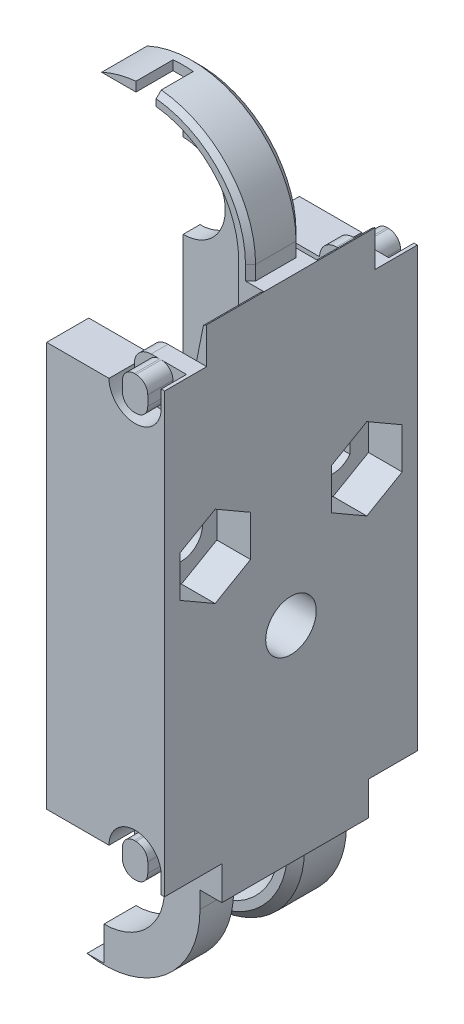
SolidWorks part; units mm, degrees
ref_plane "前视基准面" through (0, 0, 0) normal (0, 0, 1) x (1, 0, 0)
ref_plane "上视基准面" through (0, 0, 0) normal (0, 1, 0) x (1, 0, 0)
ref_plane "右视基准面" through (0, 0, 0) normal (1, 0, 0) x (0, 0, -1)
other "Configuration Table"
sketch "草图1" plane through (0, 0, 0) normal (0, 0, 1) x (1, 0, 0)
  line L0 (6.2, 9) -> (6.2, 0) construction
  line L1 (0, 0) -> (12.4, 0)
  line L2 (0, 0) -> (0, 9)
  line L4 (12.4, 0) -> (12.4, 9)
  arc A0 (0, 9) -> (12.4, 9) centre (6.2, 9) cw
  circle A1 centre (6.2, 9) radius 2.5
  circle A2 centre (1.95, 3.5) radius 0.65
  circle A3 centre (10.45, 3.5) radius 0.65
  dimension "D1" = 12.4
  dimension "D3" = 5
  dimension "D4" = 1.3
  dimension "D2" = 9
  dimension "D5" = 8.5
  dimension "D6" = 5.5
extrude "凸台-拉伸1" add sketch "草图1" along normal blind 1
sketch "草图2" plane through (0, 0, 1) normal (0, 0, 1) x (1, 0, 0)
  line L0 (0.7, 9) -> (0.7, 0)
  line L1 (0, 0) -> (12.4, 0) construction
  line L2 (11.7, 9) -> (11.7, 0)
  line L6 (0, 9) -> (0, 0)
  line L7 (0, 0) -> (12.4, 0)
  line L8 (12.4, 0) -> (12.4, 9)
  line L9 (0, 9) -> (0, 0)
  line L10 (0, 0) -> (12.4, 0)
  line L11 (12.4, 0) -> (12.4, 9)
  circle A0 centre (6.2, 9) radius 5.5
  arc A2 (12.4, 9) -> (0, 9) centre (6.2, 9) ccw
  arc A3 (12.4, 9) -> (0, 9) centre (6.2, 9) ccw
  line M5 (0, 9) -> (0, 0)
  line M6 (0, 0) -> (12.4, 0)
  line M7 (12.4, 0) -> (12.4, 9)
  arc M8 (12.4, 9) -> (0, 9) centre (6.2, 9) ccw
  dimension "D1" = 11
  dimension "D2" = 0
extrude "凸台-拉伸2" add sketch "草图2" along normal blind 2.2 contours A0 L2 L0 M6 M7 M8 M5 region at (0.5038, 4.5, 1)
sketch "草图3" plane through (0, 0, 3.2) normal (0, 0, 1) x (1, 0, 0)
  line L0 (6.2, 0) -> (6.2, 14.5) construction
  line L1 (5.6, 15.6668) -> (6.8, 15.6668)
  line L2 (5.6, 15.6668) -> (5.6, 13.6792)
  line L3 (5.6, 13.6792) -> (6.8, 13.6792)
  line L4 (6.8, 15.6668) -> (6.8, 13.6792)
  line L5 (0.7, 0) -> (11.7, 0) construction
  arc A0 (11.7, 9) -> (0.7, 9) centre (6.2, 9) ccw construction
  dimension "D1" = 1.2
extrude "切除-拉伸1" cut sketch "草图3" against normal up to surface (2.2 mm away) up to face at (6.2, 5.875, 1)
sketch "草图16" plane through (0, 0, 3.2) normal (0, 0, 1) x (1, 0, 0)
  line L0 (6.2, 0) -> (6.2, 15.1709) construction
  line L2 (13.2, 0) -> (-0.8, 0)
  line L3 (13.2, 0) -> (13.2, 5)
  line L4 (13.2, 5) -> (-0.8, 5)
  line L5 (6.8, 14.4672) -> (6.8, 15.1709)
  line L6 (5.6, 15.1709) -> (5.6, 14.4672)
  line L7 (0.7, 9) -> (0.7, 0)
  line L8 (0.7, 0) -> (11.7, 0)
  line L9 (11.7, 0) -> (11.7, 9)
  line L10 (6.8, 14.4672) -> (6.8, 15.1709)
  line L11 (5.6, 15.1709) -> (5.6, 14.4672)
  line L12 (0.7, 9) -> (0.7, 0)
  line L13 (0.7, 0) -> (11.7, 0)
  line L14 (11.7, 0) -> (11.7, 9)
  line L15 (-0.8, 0) -> (-0.8, 5)
  line L16 (-0.8, 0) -> (13.2, 0)
  line L17 (-0.8, 0) -> (-0.8, -19)
  line L18 (-0.8, -19) -> (13.2, -19)
  line L19 (13.2, 0) -> (13.2, -19)
  arc A3 (11.7, 9) -> (6.8, 14.4672) centre (6.2, 9) ccw
  arc A4 (6.8, 15.1709) -> (5.6, 15.1709) centre (6.2, 9) ccw
  arc A5 (5.6, 14.4672) -> (0.7, 9) centre (6.2, 9) ccw
  arc A6 (11.7, 9) -> (6.8, 14.4672) centre (6.2, 9) ccw
  arc A7 (6.8, 15.1709) -> (5.6, 15.1709) centre (6.2, 9) ccw
  arc A8 (5.6, 14.4672) -> (0.7, 9) centre (6.2, 9) ccw
  line M18 (11.7, 0) -> (12.4, 0)
  line M19 (12.4, 0) -> (12.4, 9)
  dimension "D2" = 5
  dimension "D3" = 14
  dimension "D4" = 19
  dimension "D1" = 0
extrude "凸台-拉伸11" add sketch "草图16" along normal blind 5.9 and the other way blind 9.1 contours L19 L2 L16 L17 L18 M18 | L15 L2 L12 L4 | L3 L4 L2 M19 region at (6.2, -9.5, 3.2) region at (12.8, 2.5, 3.2) region at (-0.05, 2.5, 3.2)
sketch "草图17" plane through (0, 0, -5.9) normal (0, 0, -1) x (-1, 0, 0)
  line L8 (-13.2, 5) -> (-13.2, -19)
  line L9 (-13.2, -19) -> (0.8, -19)
  line L10 (0.8, -19) -> (0.8, 5)
  line L11 (0.8, 5) -> (-0.7, 5)
  line L12 (-0.7, 5) -> (-0.7, 0)
  line L13 (-0.7, 0) -> (-12.4, 0)
  line L14 (-12.4, 0) -> (-12.4, 5)
  line L15 (-12.4, 5) -> (-13.2, 5)
  line L16 (-13.2, 5) -> (-13.2, -19)
  line L17 (-13.2, -19) -> (0.8, -19)
  line L18 (0.8, -19) -> (0.8, 5)
  line L19 (0.8, 5) -> (-0.7, 5)
  line L20 (-0.7, 5) -> (-0.7, 0)
  line L21 (-0.7, 0) -> (-12.4, 0)
  line L22 (-12.4, 0) -> (-12.4, 5)
  line L23 (-12.4, 5) -> (-13.2, 5)
  arc A1 (-11.9, 9) -> (-0.5, 9) centre (-6.2, 9) ccw
  circle A2 centre (-6.2, 9) radius 7.7
  line M14 (-0.7, 0) -> (-12.4, 0)
  line M15 (-12.4, 0) -> (-12.4, 5)
  dimension "D1" = 2
  dimension "D2" = 0
extrude "凸台-拉伸12" add sketch "草图17" against normal up to surface (5.9 mm away) contours A2 L20 M15 M14 region at (6.8572, 1.2193, -5.9) up to face at (5.5143, 5.6, 0)
sketch "草图18" plane through (0, 0, 9.1) normal (0, 0, 1) x (1, 0, 0)
  line L8 (13.2, -19) -> (13.2, 5)
  line L9 (13.2, 5) -> (12.4, 5)
  line L10 (12.4, 5) -> (12.4, 0)
  line L11 (12.4, 0) -> (0.7, 0)
  line L12 (0.7, 0) -> (0.7, 5)
  line L13 (0.7, 5) -> (-0.8, 5)
  line L14 (-0.8, 5) -> (-0.8, -19)
  line L15 (-0.8, -19) -> (13.2, -19)
  line L16 (13.2, -19) -> (13.2, 5)
  line L17 (13.2, 5) -> (12.4, 5)
  line L18 (12.4, 5) -> (12.4, 0)
  line L19 (12.4, 0) -> (0.7, 0)
  line L20 (0.7, 0) -> (0.7, 5)
  line L21 (0.7, 5) -> (-0.8, 5)
  line L22 (-0.8, 5) -> (-0.8, -19)
  line L23 (-0.8, -19) -> (13.2, -19)
  arc A1 (0.5, 9) -> (11.9, 9) centre (6.2, 9) ccw
  circle A2 centre (6.2, 9) radius 7.7
  line M12 (12.4, 0) -> (0.7, 0)
  line M13 (0.7, 0) -> (0.7, 5)
  dimension "D1" = 2
  dimension "D2" = 0
extrude "凸台-拉伸13" add sketch "草图18" against normal blind 5.1 contours A2 L18 M13 M12 region at (6.8572, 1.2193, 9.1)
sketch "草图19" plane through (-0.8, 0, 0) normal (-1, 0, 0) x (0, 0, 1)
  line L0 (-5.9, 4.4338) -> (-5.9, 1.3) construction
  line L1 (-5.9, 5) -> (-3.4, 5)
  line L2 (-5.9, 5) -> (-5.9, 1.3)
  line L3 (-5.9, 1.3) -> (-3.4, 1.3)
  line L4 (-3.4, 5) -> (-3.4, 1.3)
  line L5 (9.1, 5) -> (6.6, 5)
  line L6 (9.1, 5) -> (9.1, 1.3)
  line L7 (9.1, 1.3) -> (6.6, 1.3)
  line L8 (6.6, 5) -> (6.6, 1.3)
  line L9 (-5.9, 4.4338) -> (-5.9, 1.3)
  line M5 (9.1, -19) -> (9.1, 5)
  line M6 (9.1, 5) -> (-5.9, 5)
  line M7 (-5.9, 5) -> (-5.9, -19)
  dimension "D1" = 2.5
  dimension "D2" = 2.5
extrude "凸台-拉伸14" add sketch "草图19" against normal up to surface (14 mm away) contours L8 L7 M6 M5 | L4 L2 L3 M6 M7 region at (-0.8, 3.15, 7.85) region at (-0.8, 3.15, -4.65) up to face at (13.2, -7, 1.6)
ref_plane "基准面2" through (0, 0, 1.6) normal (0, 0, -1) x (-1, 0, 0)
sketch "草图21" plane through (0, 0, 1.6) normal (0, 0, -1) x (-1, 0, 0)
  line L0 (0.8, -19) -> (-13.2, -19) construction
  line L1 (-11.9, -19) -> (-0.5, -19)
  line L2 (-11.9, -19) -> (-11.9, -23)
  line L4 (-0.5, -19) -> (-0.5, -23)
  line L5 (-6.2, -19) -> (-6.2, 5) construction
  line L9 (0.8, 5) -> (-13.2, 5)
  line L10 (-13.2, 5) -> (-13.2, -19)
  line L11 (-13.2, -19) -> (0.8, -19)
  line L12 (0.8, -19) -> (0.8, 5)
  line L13 (0.8, 5) -> (-13.2, 5)
  line L14 (-13.2, 5) -> (-13.2, -19)
  line L15 (-13.2, -19) -> (0.8, -19)
  line L16 (0.8, -19) -> (0.8, 5)
  arc A0 (-11.9, -23) -> (-0.5, -23) centre (-6.2, -23) ccw
  circle A1 centre (-6.2, -23) radius 3.6
  dimension "D4" = 7.2
  dimension "D2" = 11.4
  dimension "D3" = 4
  dimension "D1" = 0
extrude "凸台-拉伸15" add sketch "草图21" along normal blind 2.5 from offset 1.6 contours L2 A0 L4 L15 L1 A1 region at (6.2, -19.1497, 1.6)
sketch "草图22" plane through (0, 0, 0) normal (0, 0, 1) x (1, 0, 0)
  circle A0 centre (6.2, -23) radius 4.2
  circle M2 centre (6.2, -23) radius 3.6
  line M4 (11.9, -19) -> (0.5, -19)
  dimension "D1" = 8.4
extrude "切除-拉伸6" cut sketch "草图22" against normal blind 0.6 and the other way blind 2.5 contours A0 M4 M2 | M2 | A0 M4 region at (3.7932, -26.2977, 0) region at (6.2, -18.9198, 0) region at (6.2, -23, 0)
chamfer "倒角2" distance 0.5 angle 45 1 edges at (6.2, -27.2, 0)
mirror "镜向1" about plane through (0, 0, 1.6) normal (0, 0, -1) of "倒角2", "切除-拉伸6", "凸台-拉伸15"
sketch "草图23" plane through (0, 0, 1.6) normal (0, 0, -1) x (-1, 0, 0)
  line L0 (-11.9, -19) -> (-0.5, -19) construction
  circle A0 centre (-6.2, -24) radius 6.2
  circle A1 centre (-6.2, -24) radius 8.2
  point P5 (-6.2, -19)
  dimension "D1" = 2
  dimension "D3" = 12.4
  dimension "D2" = 5
extrude "切除-拉伸7" cut sketch "草图23" against normal mid plane 3.2 contours A0 | A1 A0 region at (6.2, -24, 1.6) region at (14.1681, -24, 1.6)
sketch "草图24" plane through (0, 0, -2.5) normal (0, 0, -1) x (-1, 0, 0)
  line L0 (-7.2, -21.2679) -> (-7.2, -24.7321)
  line L3 (-11.9, -19) -> (-11.9, -23)
  line L4 (-0.5, -23) -> (-0.5, -19)
  line L5 (-0.5, -19) -> (-11.9, -19)
  line L6 (-11.9, -19) -> (-11.9, -23)
  line L7 (-0.5, -23) -> (-0.5, -19)
  line L8 (-0.5, -19) -> (-11.9, -19)
  circle A0 centre (-6.2, -23) radius 3.6 construction
  arc A1 (-11.9, -23) -> (-0.5, -23) centre (-6.2, -23) ccw
  arc A2 (-11.9, -23) -> (-0.5, -23) centre (-6.2, -23) ccw
  circle A3 centre (-6.2, -23) radius 3.6
  circle A4 centre (-6.2, -23) radius 2
  point P11 (-7.2, -23)
  circle M6 centre (-6.2, -23) radius 3.6
  line M7 (-11.9, -19) -> (-11.9, -23)
  arc M8 (-11.9, -23) -> (-0.5, -23) centre (-6.2, -23) ccw
  line M9 (-0.5, -23) -> (-0.5, -19)
  line M10 (-0.5, -19) -> (-11.9, -19)
  dimension "D2" = 4
  dimension "D3" = 1
  dimension "D1" = 0
extrude "凸台-拉伸16" add sketch "草图24" along normal blind 0.5 contours M10 M7 M8 M9 M6 | A4 M6 | L0 A4 region at (7.61, -23, -2.5) region at (6.2, -19.1497, -2.5) region at (9.6982, -23, -2.5)
ref_plane "基准面3" through (0, 0, 1.6) normal (0, 0, -1) x (-1, 0, 0)
chamfer "倒角4" distance 2 angle 45 2 edges at (-0.8, 5, 1.6) (-0.8, -19, 1.6)
sketch "草图25" plane through (-0.8, 0, 0) normal (-1, 0, 0) x (0, 0, 1)
  line L0 (1.6, -14) -> (1.6, 0) construction
  line L1 (9.1, -7) -> (1.6, -7) construction
  line L2 (5.7, -18.3) -> (3.2, -18.3) construction
  line L3 (5.7, -18.3) -> (3.2, -18.3)
  line L4 (9.1, -17) -> (9.1, 3)
  line L5 (9.1, 3) -> (-5.9, 3)
  line L6 (-5.9, 3) -> (-5.9, -17)
  line L8 (9.1, -17) -> (9.1, 3)
  line L10 (-5.9, 3) -> (-5.9, -17)
  line L12 (4.45, -18.3) -> (4.45, -7) construction
  line L21 (9.1, 3) -> (-5.9, 3)
  line L23 (-5.9, -17) -> (9.1, -17)
  line L24 (-5.9, -17) -> (9.1, -17)
  circle A0 centre (6.1, -4) radius 1.7
  circle A1 centre (-2.9, -4) radius 1.7
  dimension "D2" = 3.4
  dimension "D3" = 7
  dimension "D4" = 3
  dimension "D1" = 0
extrude "切除-拉伸8" cut sketch "草图25" against normal blind 2 contours A1 | A0 region at (-0.8, -4, 6.1) region at (-0.8, -4, -2.9)
sketch "草图26" plane through (1.2, 0, 0) normal (-1, 0, 0) x (0, 0, 1)
  circle A0 centre (6.1, -4) radius 0.95
  circle A1 centre (-2.9, -4) radius 0.95
  dimension "D1" = 1.9
extrude "切除-拉伸9" cut sketch "草图26" against normal through all
sketch "草图27" plane through (13.2, 0, 0) normal (1, 0, 0) x (0, 0, -1)
  line L0 (5.9, 5) -> (5.9, -19) construction
  line L1 (-6.1, -6.4249) -> (-4, -5.2124)
  line L2 (-4, -5.2124) -> (-4, -2.7876)
  line L3 (-4, -2.7876) -> (-6.1, -1.5751)
  line L4 (-6.1, -1.5751) -> (-8.2, -2.7876)
  line L5 (-8.2, -2.7876) -> (-8.2, -5.2124)
  line L6 (-8.2, -5.2124) -> (-6.1, -6.4249)
  line L7 (2.9, -6.4249) -> (5, -5.2124)
  line L8 (5, -5.2124) -> (5, -2.7876)
  line L9 (5, -2.7876) -> (2.9, -1.5751)
  line L10 (2.9, -1.5751) -> (0.8, -2.7876)
  line L11 (0.8, -2.7876) -> (0.8, -5.2124)
  line L12 (0.8, -5.2124) -> (2.9, -6.4249)
  circle A0 centre (-6.1, -4) radius 2.1 construction
  circle A1 centre (2.9, -4) radius 2.1 construction
  dimension "D1" = 4.2
extrude "切除-拉伸10" cut sketch "草图27" against normal blind 2
ref_plane "基准面4" through (0, 0, 1.6) normal (0, 0, 1) x (1, 0, 0)
sketch "草图30" plane through (0, 0, 9.1) normal (0, 0, 1) x (1, 0, 0)
  line L0 (-0.8, -7) -> (13.2, -7) construction
  line L1 (13.2, -28.6104) -> (6.2, -28.6104)
  line L2 (13.2, -28.6104) -> (13.2, 14.6104)
  line L3 (13.2, 14.6104) -> (6.2, 14.6104)
  line L4 (6.2, -28.6104) -> (6.2, 14.6104)
  line L6 (13.2, 5) -> (1.2, 5)
  line L8 (-0.8, 3) -> (-0.8, -17)
  line L10 (1.2, -19) -> (13.2, -19)
  line L11 (13.2, -19) -> (13.2, 5)
  line L12 (13.2, 5) -> (1.2, 5)
  line L14 (-0.8, 3) -> (-0.8, -17)
  line L16 (1.2, -19) -> (13.2, -19)
  line L17 (13.2, -19) -> (13.2, 5)
  line L18 (13.2, -28.6104) -> (-7.3517, -28.6104)
  line L19 (13.2, -28.6104) -> (13.2, 14.6104)
  line L20 (13.2, 14.6104) -> (-7.3517, 14.6104)
  line L21 (-7.3517, -28.6104) -> (-7.3517, 14.6104)
  line L25 (1.2, 5) -> (-0.8, 3)
  line L27 (1.2, 5) -> (-0.8, 3)
  line L29 (-0.8, -17) -> (1.2, -19)
  line L30 (-0.8, -17) -> (1.2, -19)
  point P12 (6.2, -7)
  line M11 (13.2, 5) -> (1.2, 5)
  line M12 (1.2, 5) -> (-0.8, 3)
  line M13 (-0.8, 3) -> (-0.8, -17)
  line M14 (-0.8, -17) -> (1.2, -19)
  line M15 (1.2, -19) -> (13.2, -19)
  dimension "D1" = 0
extrude "切除-拉伸11" cut sketch "草图30" against normal through all contours L21 L18 L4 L14 L20 M15 M14 M13 M12 M11 | L0 L4 M13 M11 M12 | L0 L14 L4 M14 M15 region at (2.7691, -1.1301, 9.1) region at (-1.8767, -7, 9.1) region at (2.7691, -12.8699, 9.1)
sketch "草图31" plane through (6.2, 0, 0) normal (-1, 0, 0) x (0, 0, 1)
  line L0 (3.2, 0) -> (1, 0) construction
  line L1 (-3.9, 0) -> (7.1, 0)
  line L2 (-3.9, 0) -> (-3.9, -13.8)
  line L3 (-3.9, -13.8) -> (7.1, -13.8)
  line L4 (7.1, 0) -> (7.1, -13.8)
  line L5 (-5.9, -19) -> (-5.9, 5) construction
  line L6 (9.1, -19) -> (9.1, 5) construction
  line L7 (3.2, -15.8) -> (0, -15.8) construction
  dimension "D1" = 2
  dimension "D2" = 2
  dimension "D3" = 2
extrude "切除-拉伸12" cut sketch "草图31" against normal blind 5
sketch "草图32" plane through (11.2, 0, 0) normal (-1, 0, 0) x (0, 0, 1)
  line L0 (1.6, 7.7) -> (1.6, -7.7) construction
  line L1 (-3.9, -13.8) -> (7.1, -13.8) construction
  circle A0 centre (1.6, -9.8) radius 1.5
  dimension "D1" = 4
  dimension "D2" = 3
extrude "切除-拉伸13" cut sketch "草图32" against normal blind 5
sketch "草图33" plane through (0, -19, 0) normal (0, -1, 0) x (1, 0, 0)
  line L0 (6.2, 9.1) -> (13.2, 9.1) construction
  line L1 (6.2, 5.7) -> (6.2, 9.1) construction
  circle A0 centre (8.5, 6.8) radius 1.4
  dimension "D1" = 2.8
  dimension "D2" = 2.3
  dimension "D3" = 2.3
extrude "切除-拉伸16" cut sketch "草图33" against normal blind 8
chamfer "倒角5" distance 1 angle 45 1 edges at (8.5, -11, 7.1)
sketch "草图35" plane through (0, 0, 9.1) normal (0, 0, 1) x (1, 0, 0)
  line L0 (12.4, 5) -> (12.4, 9)
  line L1 (12.4, 9) -> (11.9, 9)
  line L2 (11.9, 9) -> (8.4, 5)
  line L3 (13.2, 5) -> (6.2, 5) construction
  line L4 (12.4, 5) -> (6.2, 5) construction
  line L5 (12.4, 5) -> (6.2, 5)
  line L6 (12.4, 9) -> (13.2, 5)
  line L7 (13.2, 5) -> (12.4, 5)
  line M6 (13.2, 5) -> (6.2, 5)
  dimension "D1" = 4
  dimension "D2" = 0.5
  dimension "D3" = 4
extrude "凸台-拉伸17" add sketch "草图35" against normal blind 2.5 contours L1 L2 L0 M6 | L6 L0 M6 region at (11.0481, 6.4815, 9.1) region at (12.6667, 6.3333, 9.1)
mirror "镜向3" about plane through (0, 0, 1.6) normal (0, 0, 1) of "凸台-拉伸17"
sketch "草图36" plane through (0, 0, 6.6) normal (0, 0, -1) x (-1, 0, 0)
  line L1 (-12.4, 9) -> (-11.9, 9) construction
  line L2 (-12.4, 9) -> (-13.2, 5) construction
  line L5 (-13.2, 5) -> (-13.2, 9)
  line L6 (-13.2, 9) -> (-12.4, 9) construction
  line L7 (-12.4, 5) -> (-13.2, 5)
  line L8 (-12.4, 5) -> (-13.2, 9)
  line L10 (-12.4, 9) -> (-12.4, 5) construction
extrude "凸台-拉伸18" add sketch "草图36" along normal up to surface (10 mm away) up to face at (10.4342, 5.3744, -3.4)
sketch "草图38" plane through (0, 0, 9.1) normal (0, 0, 1) x (1, 0, 0)
  line L0 (13.2, -19) -> (13.2, -22)
  line L1 (13.2, -22) -> (12.2, -22)
  line L2 (12.2, -22) -> (9.7, -19)
  line L3 (6.2, -19) -> (13.2, -19) construction
  line L4 (13.2, -19) -> (9.7, -19)
  line M4 (6.2, -19) -> (13.2, -19)
  dimension "D1" = 1
  dimension "D2" = 3
extrude "凸台-拉伸19" add sketch "草图38" against normal blind 3.4 contours L2 L1 L0 M4 region at (11.9593, -20.2222, 9.1)
mirror "镜向6" about plane through (0, 0, 1.6) normal (0, 0, 1) of "凸台-拉伸19"
sketch "草图39" plane through (0, 0, 5.7) normal (0, 0, -1) x (-1, 0, 0)
  line L0 (-11.9, -19) -> (-13.2, -19)
  line L1 (-13.2, -19) -> (-13.2, -22)
  line L2 (-13.2, -22) -> (-11.9, -19)
extrude "凸台-拉伸20" add sketch "草图39" along normal up to surface (8.2 mm away) up to face at (12.48, -20.728, -2.5)
sketch "草图40" plane through (0, 5, 0) normal (0, 1, 0) x (1, 0, 0)
  line L1 (8.4, -6.6) -> (16.8775, -6.6)
  line L2 (8.4, -6.6) -> (8.4, -9.6779)
  line L3 (8.4, -9.6779) -> (16.8775, -9.6779)
  line L4 (16.8775, -6.6) -> (16.8775, -9.6779)
  line L5 (8.4, 3.4) -> (14.8256, 3.4)
  line L6 (8.4, 3.4) -> (8.4, 6.7357)
  line L7 (8.4, 6.7357) -> (14.8256, 6.7357)
  line L8 (14.8256, 3.4) -> (14.8256, 6.7357)
extrude "切除-拉伸17" cut sketch "草图40" along normal up to surface (4 mm away) up to face at (12.15, 9, 7.85)
sketch "草图42" plane through (0, -19, 0) normal (0, -1, 0) x (1, 0, 0)
  line L1 (9.7, -3) -> (14.9483, -3)
  line L2 (9.7, -3) -> (9.7, -6.6318)
  line L3 (9.7, -6.6318) -> (14.9483, -6.6318)
  line L4 (14.9483, -3) -> (14.9483, -6.6318)
  line L5 (9.7, 5.7) -> (16.4897, 5.7)
  line L6 (9.7, 5.7) -> (9.7, 10.2612)
  line L7 (9.7, 10.2612) -> (16.4897, 10.2612)
  line L8 (16.4897, 5.7) -> (16.4897, 10.2612)
extrude "切除-拉伸18" cut sketch "草图42" along normal up to surface (3 mm away) up to face at (12.7, -22, 7.4)
sketch "草图43" plane through (0, 0, 9.1) normal (0, 0, 1) x (1, 0, 0)
  line L0 (7.1, -19) -> (9.9, -19) construction
  line L1 (7.1, -19) -> (9.9, -19)
  line L3 (10.7, -19) -> (12.2, -19)
  line L4 (6.2, -19) -> (13.2, -19)
  line L5 (13.2, -19) -> (13.2, 5)
  line L6 (13.2, 5) -> (6.2, 5)
  line L7 (6.2, 5) -> (6.2, -19)
  line L8 (6.2, -19) -> (13.2, -19)
  line L9 (13.2, -19) -> (13.2, 5)
  line L10 (13.2, 5) -> (6.2, 5)
  line L11 (6.2, 5) -> (6.2, -19)
  line L12 (10.7, -19) -> (10.7, -18.7)
  line L13 (11.4, -18) -> (11.5, -18)
  line L14 (12.2, -19) -> (12.2, -18.7)
  arc A0 (11.5, -18) -> (12.2, -18.7) centre (11.5, -18.7) cw
  arc A1 (10.7, -18.7) -> (11.4, -18) centre (11.4, -18.7) cw
  arc A2 (9.9, -19) -> (13, -19) centre (11.45, -19) cw
  point P12 (12.2, -18)
  point P15 (10.7, -18)
  line M7 (6.2, -19) -> (13.2, -19)
  dimension "D5" = 0.7
  dimension "D2" = 1
  dimension "D3" = 1.5
  dimension "D4" = 1
  dimension "D1" = 0
extrude "切除-拉伸19" cut sketch "草图43" against normal blind 1.5 contours A2 L12 A1 L13 A0 L14 M7 region at (11.45, -17.4847, 9.1)
mirror "镜向7" about plane through (0, 0, 1.6) normal (0, 0, -1) of "切除-拉伸19"
ref_plane "基准面5" through (0, -7, 0) normal (0, 1, 0) x (1, 0, 0)
mirror "镜向8" about plane through (0, -7, 0) normal (0, 1, 0) of "镜向7", "切除-拉伸19"
chamfer "倒角6" distance 0.5 angle 45 4 edges at (11.9, -21, 3.2) (9.8573, -27.372, 3.2) (11.9, -21, 0) (9.8573, -27.372, 0)
chamfer "倒角7" distance 0.5 angle 45 2 edges at (6.8481, -18.8503, 3.2) (6.8481, -18.8503, 0)
chamfer "倒角8" distance 0.3 angle 45 2 edges at (12.4, 7, 3.2) (10.7913, 13.1665, 3.2)
chamfer "倒角9" distance 0.5 angle 45 2 edges at (12.4, 7, 0) (9.5226, 14.2346, 0)
chamfer "倒角10" distance 1 angle 45 1 edges at (13.2, 9, 1.6) first distance on face at (12.5625, 5.8125, 2.025)
sketch "草图44" plane through (0, 5, 0) normal (0, 1, 0) x (1, 0, 0)
  line L0 (13.2, 5.9) -> (13, 5.9) construction
  line L1 (13, 5.9) -> (13, 4.4) construction
  line L2 (13, 4.4) -> (12.2, 4.4) construction
  line L3 (12.2, 4.4) -> (12.2, 5.9) construction
  line L4 (12.2, 5.9) -> (10.7, 5.9) construction
  line L5 (10.7, 5.9) -> (10.7, 4.4) construction
  line L6 (10.7, 4.4) -> (9.9, 4.4) construction
  line L7 (9.9, 4.4) -> (9.9, 5.9) construction
  line L8 (9.9, 5.9) -> (6.2, 5.9) construction
  line L9 (6.2, 5.9) -> (6.2, 3.4) construction
  line L10 (6.2, 3.4) -> (12.4, 3.4) construction
  line L11 (12.4, 3.4) -> (13.2, 3.4) construction
  line L12 (13.2, 3.4) -> (13.2, 5.9) construction
  line L13 (9.9, -9.1) -> (9.9, -7.6) construction
  line L14 (9.9, -7.6) -> (10.7, -7.6) construction
  line L15 (10.7, -7.6) -> (10.7, -9.1) construction
  line L16 (10.7, -9.1) -> (12.2, -9.1) construction
  line L17 (12.2, -9.1) -> (12.2, -7.6) construction
  line L18 (12.2, -7.6) -> (13, -7.6) construction
  line L19 (13, -7.6) -> (13, -9.1) construction
  line L20 (13, -9.1) -> (13.2, -9.1) construction
  line L21 (13.2, -9.1) -> (13.2, -6.6) construction
  line L22 (13.2, -6.6) -> (12.4, -6.6) construction
  line L23 (12.4, -6.6) -> (6.2, -6.6) construction
  line L24 (6.2, -6.6) -> (6.2, -9.1) construction
  line L25 (6.2, -9.1) -> (9.9, -9.1) construction
  line L26 (13.2, 5.9) -> (13, 5.9)
  line L27 (13, 5.9) -> (13, 4.4)
  line L28 (13, 4.4) -> (12.2, 4.4)
  line L29 (12.2, 4.4) -> (12.2, 5.9)
  line L30 (12.2, 5.9) -> (10.7, 5.9)
  line L31 (10.7, 5.9) -> (10.7, 4.4)
  line L32 (10.7, 4.4) -> (9.9, 4.4)
  line L33 (9.9, 4.4) -> (9.9, 5.9)
  line L34 (9.9, 5.9) -> (6.2, 5.9)
  line L35 (6.2, 5.9) -> (6.2, 3.4)
  line L36 (6.2, 3.4) -> (12.4, 3.4)
  line L37 (12.4, 3.4) -> (13.2, 3.4)
  line L38 (13.2, 3.4) -> (13.2, 5.9)
  line L39 (9.9, -9.1) -> (9.9, -7.6)
  line L40 (9.9, -7.6) -> (10.7, -7.6)
  line L41 (10.7, -7.6) -> (10.7, -9.1)
  line L42 (10.7, -9.1) -> (12.2, -9.1)
  line L43 (12.2, -9.1) -> (12.2, -7.6)
  line L44 (12.2, -7.6) -> (13, -7.6)
  line L45 (13, -7.6) -> (13, -9.1)
  line L46 (13, -9.1) -> (13.2, -9.1)
  line L47 (13.2, -9.1) -> (13.2, -6.6)
  line L48 (13.2, -6.6) -> (12.4, -6.6)
  line L49 (12.4, -6.6) -> (6.2, -6.6)
  line L50 (6.2, -6.6) -> (6.2, -9.1)
  line L51 (6.2, -9.1) -> (9.9, -9.1)
  line L52 (9.9, -7.6) -> (9.9, -6.6)
  line L53 (9.9, 4.4) -> (9.9, 3.4)
  line M2 (9.9, -7.6) -> (10.7, -7.6)
  line M3 (10.7, -7.6) -> (10.7, -9.1)
  line M4 (10.7, -9.1) -> (12.2, -9.1)
  line M5 (12.2, -9.1) -> (12.2, -7.6)
  line M6 (12.2, -7.6) -> (13, -7.6)
  line M7 (13, -7.6) -> (13, -9.1)
  line M8 (13, -9.1) -> (13.2, -9.1)
  line M9 (13.2, -9.1) -> (13.2, -6.6)
  line M10 (13.2, -6.6) -> (12.4, -6.6)
  line M11 (12.4, -6.6) -> (6.2, -6.6)
extrude "凸台-拉伸21" add sketch "草图44" along normal blind 1 contours L52 M2 M3 M4 M5 M6 M7 M8 M9 M10 M11 | L32 L53 L36 L37 L38 L26 L27 L28 L29 L30 L31 region at (11.591, 5, -4.4449) region at (11.591, 5, 7.6449)
sketch "草图45" plane through (0, -19, 0) normal (0, -1, 0) x (1, 0, 0)
  line L0 (9.9, -5.9) -> (9.9, -4.4) construction
  line L1 (9.9, -4.4) -> (10.7, -4.4) construction
  line L2 (10.7, -4.4) -> (10.7, -5.9) construction
  line L3 (10.7, -5.9) -> (12.2, -5.9) construction
  line L4 (12.2, -5.9) -> (12.2, -4.4) construction
  line L5 (12.2, -4.4) -> (13, -4.4) construction
  line L6 (13, -4.4) -> (13, -5.9) construction
  line L7 (13, -5.9) -> (13.2, -5.9) construction
  line L8 (13.2, -5.9) -> (13.2, -3) construction
  line L9 (13.2, -3) -> (6.2, -3) construction
  line L10 (6.2, -3) -> (6.2, -5.9) construction
  line L11 (6.2, -5.9) -> (9.9, -5.9) construction
  line L12 (13.2, 9.1) -> (13, 9.1) construction
  line L13 (13, 9.1) -> (13, 7.6) construction
  line L14 (13, 7.6) -> (12.2, 7.6) construction
  line L15 (12.2, 7.6) -> (12.2, 9.1) construction
  line L16 (12.2, 9.1) -> (10.7, 9.1) construction
  line L17 (10.7, 9.1) -> (10.7, 7.6) construction
  line L18 (10.7, 7.6) -> (9.9, 7.6) construction
  line L19 (9.9, 7.6) -> (9.9, 9.1) construction
  line L20 (9.9, 9.1) -> (6.2, 9.1) construction
  line L21 (6.2, 9.1) -> (6.2, 5.7) construction
  line L22 (6.2, 5.7) -> (7.634, 5.7) construction
  line L23 (9.366, 5.7) -> (11.9, 5.7) construction
  line L24 (11.9, 5.7) -> (13.2, 5.7) construction
  line L25 (13.2, 5.7) -> (13.2, 9.1) construction
  line L26 (9.9, -5.9) -> (9.9, -4.4)
  line L27 (9.9, -4.4) -> (10.7, -4.4)
  line L28 (10.7, -4.4) -> (10.7, -5.9)
  line L29 (10.7, -5.9) -> (12.2, -5.9)
  line L30 (12.2, -5.9) -> (12.2, -4.4)
  line L31 (12.2, -4.4) -> (13, -4.4)
  line L32 (13, -4.4) -> (13, -5.9)
  line L33 (13, -5.9) -> (13.2, -5.9)
  line L34 (13.2, -5.9) -> (13.2, -3)
  line L35 (13.2, -3) -> (6.2, -3)
  line L36 (6.2, -3) -> (6.2, -5.9)
  line L37 (6.2, -5.9) -> (9.9, -5.9)
  line L38 (13.2, 9.1) -> (13, 9.1)
  line L39 (13, 9.1) -> (13, 7.6)
  line L40 (13, 7.6) -> (12.2, 7.6)
  line L41 (12.2, 7.6) -> (12.2, 9.1)
  line L42 (12.2, 9.1) -> (10.7, 9.1)
  line L43 (10.7, 9.1) -> (10.7, 7.6)
  line L44 (10.7, 7.6) -> (9.9, 7.6)
  line L45 (9.9, 7.6) -> (9.9, 9.1)
  line L46 (9.9, 9.1) -> (6.2, 9.1)
  line L47 (6.2, 9.1) -> (6.2, 5.7)
  line L48 (6.2, 5.7) -> (7.634, 5.7)
  line L49 (9.366, 5.7) -> (11.9, 5.7)
  line L50 (11.9, 5.7) -> (13.2, 5.7)
  line L51 (13.2, 5.7) -> (13.2, 9.1)
  line L52 (9.9, -4.4) -> (9.9, -3)
  line L54 (9.9, 7.6) -> (9.9, 5.7)
  arc A0 (9.366, 5.7) -> (7.634, 5.7) centre (8.5, 6.8) ccw construction
  arc A1 (9.366, 5.7) -> (7.634, 5.7) centre (8.5, 6.8) ccw
  line M2 (13.2, 9.1) -> (13, 9.1)
  line M3 (13, 9.1) -> (13, 7.6)
  line M4 (13, 7.6) -> (12.2, 7.6)
  line M5 (12.2, 7.6) -> (12.2, 9.1)
  line M6 (12.2, 9.1) -> (10.7, 9.1)
  line M7 (10.7, 9.1) -> (10.7, 7.6)
  line M8 (10.7, 7.6) -> (9.9, 7.6)
  line M15 (11.9, 5.7) -> (13.2, 5.7)
  line M16 (13.2, 5.7) -> (13.2, 9.1)
extrude "凸台-拉伸22" add sketch "草图45" along normal blind 1 contours L52 L27 L28 L29 L30 L31 L32 L33 L34 L35 | L54 L49 M8 M15 M16 M2 M3 M4 M5 M6 M7 region at (11.5835, -19, -4.2157) region at (11.5772, -19, 7.1415)
fillet "圆角1" radius 1 4 edges at (9.9, 6, -3.9) (9.9, 6, 7.1) (9.9, -20, 6.65) (9.9, -20, -3.7)
fillet "圆角2" radius 0.7 8 edges at (10.7, -19.9798, -5.15) (12.2, -20, -5.15) (12.2, -20, 8.35) (10.7, -19.9798, 8.35) (10.7, 5.9798, 8.35) (12.2, 6, 8.35) (12.2, 6, -5.15) (10.7, 5.9798, -5.15)
sketch "草图46" plane through (11.2, 0, 0) normal (-1, 0, 0) x (0, 0, 1)
  line L0 (-2.9, -1.5751) -> (-2.9, -6.4249)
  line L1 (6.1, -1.5751) -> (6.1, -6.4249)
  line L2 (7.1, -2.1525) -> (7.1, -5.8475)
  line L3 (-3.9, -2.1525) -> (-3.9, -5.8475)
  line L18 (7.1, -5.8475) -> (6.1, -6.4249)
  line L19 (6.1, -6.4249) -> (4, -5.2124)
  line L20 (4, -5.2124) -> (4, -2.7876)
  line L21 (4, -2.7876) -> (6.1, -1.5751)
  line L22 (6.1, -1.5751) -> (7.1, -2.1525)
  line L23 (7.1, -2.1525) -> (7.1, 0)
  line L24 (7.1, 0) -> (4, 0)
  line L25 (4, 0) -> (1, 0)
  line L26 (1, 0) -> (-3.9, 0)
  line L27 (-3.9, 0) -> (-3.9, -2.1525)
  line L28 (-3.9, -2.1525) -> (-2.9, -1.5751)
  line L29 (-2.9, -1.5751) -> (-0.8, -2.7876)
  line L30 (-0.8, -2.7876) -> (-0.8, -5.2124)
  line L31 (-0.8, -5.2124) -> (-2.9, -6.4249)
  line L32 (-2.9, -6.4249) -> (-3.9, -5.8475)
  line L33 (-3.9, -5.8475) -> (-3.9, -13.8)
  line L34 (-3.9, -13.8) -> (7.1, -13.8)
  line L35 (7.1, -13.8) -> (7.1, -5.8475)
  line L36 (7.1, -5.8475) -> (6.1, -6.4249)
  line L37 (6.1, -6.4249) -> (4, -5.2124)
  line L38 (4, -5.2124) -> (4, -2.7876)
  line L39 (4, -2.7876) -> (6.1, -1.5751)
  line L40 (6.1, -1.5751) -> (7.1, -2.1525)
  line L41 (7.1, -2.1525) -> (7.1, 0)
  line L42 (7.1, 0) -> (4, 0)
  line L43 (4, 0) -> (1, 0)
  line L44 (1, 0) -> (-3.9, 0)
  line L45 (-3.9, 0) -> (-3.9, -2.1525)
  line L46 (-3.9, -2.1525) -> (-2.9, -1.5751)
  line L47 (-2.9, -1.5751) -> (-0.8, -2.7876)
  line L48 (-0.8, -2.7876) -> (-0.8, -5.2124)
  line L49 (-0.8, -5.2124) -> (-2.9, -6.4249)
  line L50 (-2.9, -6.4249) -> (-3.9, -5.8475)
  line L51 (-3.9, -5.8475) -> (-3.9, -13.8)
  line L52 (-3.9, -13.8) -> (7.1, -13.8)
  line L53 (7.1, -13.8) -> (7.1, -5.8475)
  circle A0 centre (-2.9, -4) radius 1.25
  circle A1 centre (6.1, -4) radius 1.25
  circle M19 centre (1.6, -9.8) radius 1.5
  line M20 (7.1, -5.8475) -> (6.1, -6.4249)
  line M21 (6.1, -6.4249) -> (4, -5.2124)
  line M22 (4, -5.2124) -> (4, -2.7876)
  line M23 (4, -2.7876) -> (6.1, -1.5751)
  line M24 (6.1, -1.5751) -> (7.1, -2.1525)
  line M25 (7.1, -2.1525) -> (7.1, 0)
  line M26 (7.1, 0) -> (4, 0)
  line M27 (4, 0) -> (1, 0)
  line M28 (1, 0) -> (-3.9, 0)
  line M29 (-3.9, 0) -> (-3.9, -2.1525)
  line M30 (-3.9, -2.1525) -> (-2.9, -1.5751)
  line M31 (-2.9, -1.5751) -> (-0.8, -2.7876)
  line M32 (-0.8, -2.7876) -> (-0.8, -5.2124)
  line M33 (-0.8, -5.2124) -> (-2.9, -6.4249)
  line M34 (-2.9, -6.4249) -> (-3.9, -5.8475)
  line M35 (-3.9, -5.8475) -> (-3.9, -13.8)
  line M36 (-3.9, -13.8) -> (7.1, -13.8)
  line M37 (7.1, -13.8) -> (7.1, -5.8475)
  dimension "D2" = 2.5
  dimension "D1" = 0
extrude "凸台-拉伸23" add sketch "草图46" along normal blind 1 contours M37 M20 M21 M22 M23 M24 M25 M26 M27 M28 M29 M30 M31 M32 M33 M34 M35 M36 M19 | A0 L0 M33 M32 M31 | A0 L0 L3 M30 | A0 L3 L0 M34 | A1 L1 M23 M22 M21 | A1 L2 L1 M24 | A1 L1 L2 M20 region at (11.2, -2.2271, -1.8764) region at (11.2, -2.3786, -3.3915) region at (11.2, -7.3018, 1.6) region at (11.2, -5.6214, -3.3915) region at (11.2, -2.3786, 6.5915) region at (11.2, -5.6214, 6.5915) region at (11.2, -2.1626, 6.0472)
ref_plane "基准面6" through (0, 8.1502, 0) normal (0, 1, 0) x (1, 0, 0)
sketch "草图47" plane through (0, 8.1502, 0) normal (0, 1, 0) x (1, 0, 0)
  line L0 (12.4, -2.9) -> (12.4, -0.5) construction
  line L1 (12.4, -2.9) -> (12.4, -0.5)
  line L2 (11.9, 0) -> (12.4, -0.5) construction
  line L3 (12.4, -2.9) -> (12.1, -3.2) construction
  line L4 (11.9, 0) -> (12.4, -0.5)
  line L5 (12.4, -2.9) -> (12.1, -3.2)
  line L6 (13.2, 3.4) -> (13.2, -6.6) construction
  line L7 (13.2, 0) -> (13.2, -3.2)
  line L8 (12.1, -3.2) -> (13.2, -3.2)
  line L10 (11.9, 0) -> (13.2, 0)
extrude "凸台-拉伸24" add sketch "草图47" against normal up to next
sketch "草图48" plane through (0, -22, 0) normal (0, -1, 0) x (1, 0, 0)
  line L0 (11.9, -3) -> (11.9, -0.5) construction
  line L1 (13.2, -3) -> (11.9, -3)
  line L2 (13.2, -3) -> (13.2, -0.5)
  line L3 (13.2, -0.5) -> (11.9, -0.5)
  line L4 (11.9, -3) -> (11.9, -0.5)
  line L6 (13.2, 5.7) -> (11.9, 5.7)
  line L7 (13.2, 5.7) -> (13.2, 3.7)
  line L8 (13.2, 3.7) -> (11.9, 3.7)
  line L9 (11.9, 5.7) -> (11.9, 3.7)
extrude "凸台-拉伸25" add sketch "草图48" against normal up to next
